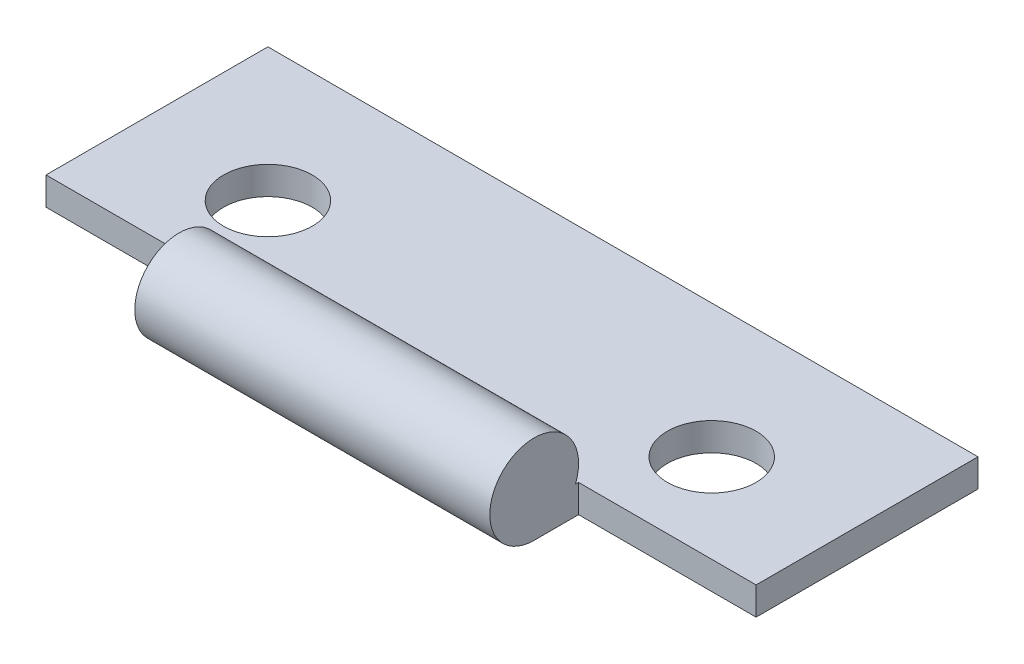
SolidWorks part; units mm, degrees
ref_plane "Front Plane" through (0, 0, 0) normal (0, 0, 1) x (1, 0, 0)
ref_plane "Top Plane" through (0, 0, 0) normal (0, 1, 0) x (1, 0, 0)
ref_plane "Right Plane" through (0, 0, 0) normal (1, 0, 0) x (0, 0, -1)
sketch "Sketch1" plane through (0, 0, 0) normal (0, 1, 0) x (1, 0, 0)
  line L0 (12.7, 9.525) -> (12.7, 0) construction
  line L1 (25.4, 9.525) -> (25.4, 1.5875)
  line L2 (0, 9.525) -> (0, 1.5875)
  line L3 (0, 9.525) -> (25.4, 9.525)
  line L4 (25.4, 1.5875) -> (19.05, 1.5875)
  line L5 (0, 1.5875) -> (6.35, 1.5875)
  line L6 (6.35, 1.5875) -> (6.35, 0)
  line L7 (6.35, 0) -> (19.05, 0)
  line L8 (19.05, 1.5875) -> (19.05, 0)
  circle A0 centre (4.7625, 4.7625) radius 1.5875
  circle A1 centre (20.6375, 4.7625) radius 1.5875
  dimension "D3" = 3.175
  dimension "D1" = 7.9375
  dimension "D2" = 25.4
  dimension "D4" = 6.35
  dimension "D5" = 1.5875
extrude "Boss-Extrude1" add sketch "Sketch1" along normal blind 1
sketch "Sketch2" plane through (6.35, 0, 0) normal (-1, 0, 0) x (0, 0, 1)
  line L1 (0, 1) -> (0, 0) construction
  circle A0 centre (0, 1.5875) radius 1.5875
  dimension "D1" = 3.175
extrude "Boss-Extrude2" add sketch "Sketch2" against normal blind 12.7
